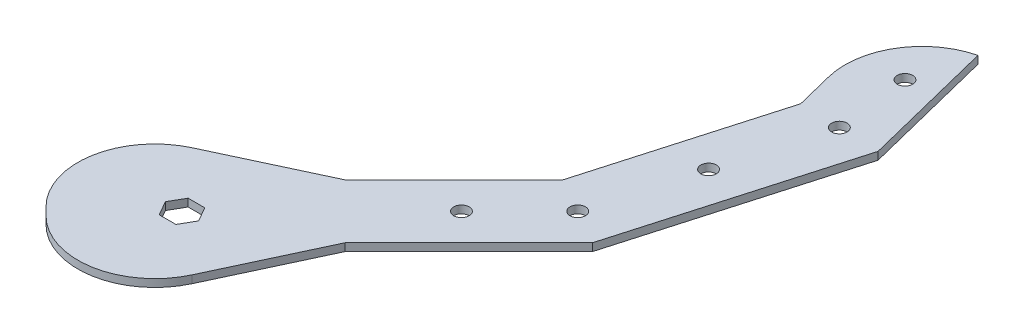
SolidWorks part; units mm, degrees
ref_plane "Front" through (0, 0, 0) normal (0, 0, 1) x (1, 0, 0)
ref_plane "Top" through (0, 0, 0) normal (0, 1, 0) x (1, 0, 0)
ref_plane "Right" through (0, 0, 0) normal (1, 0, 0) x (0, 0, -1)
sketch "Sketch1" plane through (0, 0, 0) normal (0, 1, 0) x (1, 0, 0)
  line L0 (38.7068, 38.7068) -> (79.551, 79.551)
  line L1 (79.551, 79.551) -> (100.5546, 152.7992)
  line L3 (74.1703, 153.6284) -> (56.6673, 92.5883)
  line L4 (56.6673, 92.5883) -> (20.7463, 56.6673)
  line L6 (0, 0) -> (65.8725, 0) construction
  line L7 (38.7068, 38.7068) -> (7.2759, -28.6451)
  line L8 (74.1703, 153.6284) -> (64.953, 190.5967)
  line L9 (64.953, 190.5967) -> (89.5986, 196.7415)
  line L10 (89.5986, 196.7415) -> (100.5546, 152.7992)
  line L11 (7.2759, -28.6451) -> (-46.6056, 25.2364)
  line L12 (-46.6056, 25.2364) -> (20.7463, 56.6673)
  line L13 (0, 0) -> (38.7068, 38.7068) construction
  line L14 (38.7068, 38.7068) -> (20.7463, 56.6673) construction
  line L16 (29.7265, 47.687) -> (-19.6649, -1.7044) construction
  line L18 (8.285, 20.7463) -> (5.5354, 25.5088)
  line L19 (5.5354, 25.5088) -> (0.0361, 25.5088)
  line L20 (0.0361, 25.5088) -> (-2.7135, 20.7463)
  line L21 (-2.7135, 20.7463) -> (0.0361, 15.9838)
  line L22 (0.0361, 15.9838) -> (5.5354, 15.9838)
  line L23 (5.5354, 15.9838) -> (8.285, 20.7463)
  circle A1 centre (-8.7161, 125.4328) radius 74.8113 construction
  arc A2 (45.0362, 177.4656) -> (-62.4685, 73.4) centre (-8.7161, 125.4328) ccw construction
  circle A3 centre (2.7858, 20.7463) radius 8.89 construction
  circle A4 centre (2.7858, 20.7463) radius 4.7625 construction
  point P7 (0, 0)
  dimension "D9" = 38.1
  dimension "D7" = 17.78
  dimension "D1" = 74
  dimension "D2" = 25.4
  dimension "D3" = 45
  dimension "D4" = 76.2
  dimension "D5" = 50.8
  dimension "D6" = 69.85
  dimension "D8" = 76.2
  dimension "D10" = 25.4
  dimension "D11" = 38.1
  dimension "D12" = 150
  dimension "D13" = 63.5
  dimension "D14" = 9.525
extrude "Boss-Extrude1" add sketch "Sketch1" along normal blind 2.54
fillet "Fillet3" radius 25.4 1 edges at (64.953, 1.27, -190.5967)
hole_wizard "#10 Clearance Hole1" positions "Sketch2" profile "Sketch3" hole size "#10" standard "ANSI Inch"
sketch "Sketch2" plane through (0, 2.54, 0) normal (0, 1, 0) x (1, 0, 0)
  line L0 (100.5546, 152.7992) -> (89.5986, 196.7415) construction
  line L1 (100.5546, 152.7992) -> (74.1703, 153.6284) construction
  line L3 (90.0528, 116.1751) -> (65.4188, 123.1084) construction
  line L4 (79.551, 79.551) -> (100.5546, 152.7992) construction
  line L5 (74.1703, 153.6284) -> (56.6673, 92.5883) construction
  line L7 (79.551, 79.551) -> (56.6673, 92.5883) construction
  line L9 (59.1289, 59.1289) -> (38.7068, 74.6278) construction
  line L10 (38.7068, 38.7068) -> (79.551, 79.551) construction
  line L12 (56.6673, 92.5883) -> (20.7463, 56.6673) construction
  point P0 (84.5317, 177.6915)
  point P2 (87.3624, 153.2138)
  point P4 (77.7358, 119.6418)
  point P6 (68.1092, 86.0697)
  point P8 (48.9179, 66.8784)
  dimension "D1" = 9.525
  dimension "D2" = 19.05
sketch "Sketch3" plane through (84.5317, 2.54, -177.6915) normal (1, 0, 0) x (0, 0, 1)
  line L0 (0, 0) -> (0, 11.4398)
  line L1 (0, 11.4398) -> (2.5527, 9.906)
  line L2 (2.5527, 9.906) -> (2.5527, 0)
  line L5 (2.5527, 0) -> (0, 0)
  line L10 (0, 11.4398) -> (-2.5527, 9.906) construction
  line L11 (0, -6.35) -> (0, 107.95) construction
  dimension "Hole Dia." = 5.1054
  dimension "Hole Depth" = 9.906
  dimension "Drill Angle" = 118
fillet "Fillet4" radius 25.4 2 edges at (7.2759, 1.27, 28.6451) (-46.6056, 1.27, -25.2364)
